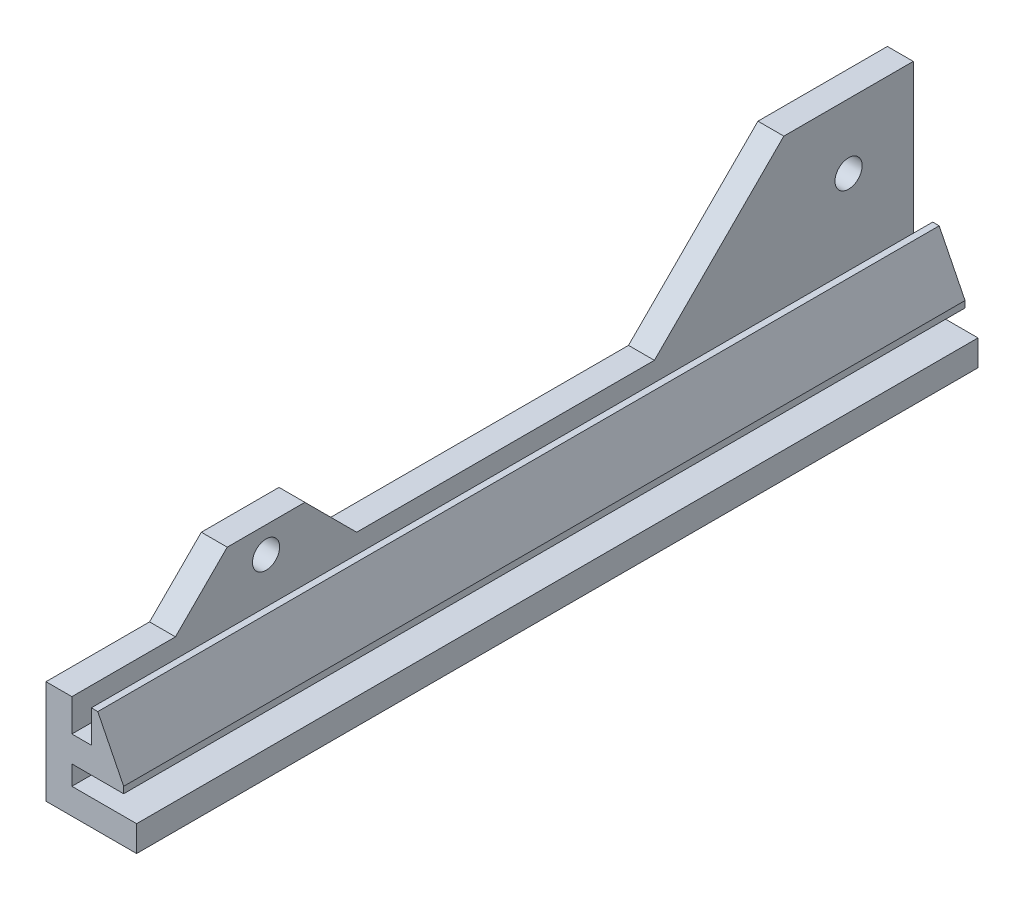
SolidWorks part; units mm, degrees
material "ABS"
ref_plane "Płaszczyzna przednia" through (0, 0, 0) normal (0, 0, 1) x (1, 0, 0)
ref_plane "Płaszczyzna górna" through (0, 0, 0) normal (0, 1, 0) x (1, 0, 0)
ref_plane "Płaszczyzna prawa" through (0, 0, 0) normal (1, 0, 0) x (0, 0, -1)
sketch "Szkic1" plane through (0, 0, 0) normal (0, 0, 1) x (1, 0, 0)
  line L0 (0, 0) -> (14, 0)
  line L1 (0, 0) -> (0, 16)
  line L2 (14, 0) -> (14, 4)
  line L3 (14, 4) -> (4, 4)
  line L4 (4, 4) -> (4, 7)
  line L5 (4, 7) -> (12, 7)
  line L6 (0, 16) -> (4, 16)
  line L7 (4, 16) -> (4, 11)
  line L8 (4, 11) -> (7, 11)
  line L9 (7, 11) -> (7, 16)
  line L11 (7, 16) -> (8, 16)
  line L12 (8, 16) -> (12, 8)
  line L13 (12, 8) -> (12, 7)
  point P12 (4, 5.5)
  dimension "D1" = 14
  dimension "D2" = 16
  dimension "D3" = 4
  dimension "D4" = 3
  dimension "D5" = 4
  dimension "D6" = 4
  dimension "D7" = 3
  dimension "D8" = 8
  dimension "D9" = 5
  dimension "D10" = 1
  dimension "D11" = 1
extrude "Dodanie-wyciągnięcie1" add sketch "Szkic1" along normal blind 130
sketch "Szkic2" plane through (0, 0, 0) normal (-1, 0, 0) x (0, 0, 1)
  line L0 (20, 36) -> (40, 16)
  line L1 (0, 16) -> (20, 16)
  line L2 (0, 16) -> (0, 36)
  line L3 (0, 36) -> (20, 36)
  line L5 (130, 16) -> (0, 16) construction
  line L6 (40, 16) -> (20, 16)
  line L7 (106, 16) -> (106, 24)
  line L8 (106, 24) -> (94, 24)
  line L9 (94, 24) -> (94, 16)
  line L10 (94, 16) -> (106, 16)
  line L11 (130, 16) -> (130, 0) construction
  circle A0 centre (10, 26) radius 2.1
  circle A1 centre (100, 20) radius 2.1
  dimension "D5" = 4.2
  dimension "D1" = 20
  dimension "D2" = 20
  dimension "D3" = 10
  dimension "D4" = 10
  dimension "D6" = 20
  dimension "D7" = 40
  dimension "D8" = 4
  dimension "D9" = 6
  dimension "D10" = 6
  dimension "D11" = 30
  dimension "D12" = 8
extrude "Dodanie-wyciągnięcie2" add sketch "Szkic2" against normal blind 4
chamfer "Sfazowanie1" distance 8 angle 45 2 edges at (2, 16, 94) (2, 16, 106)
